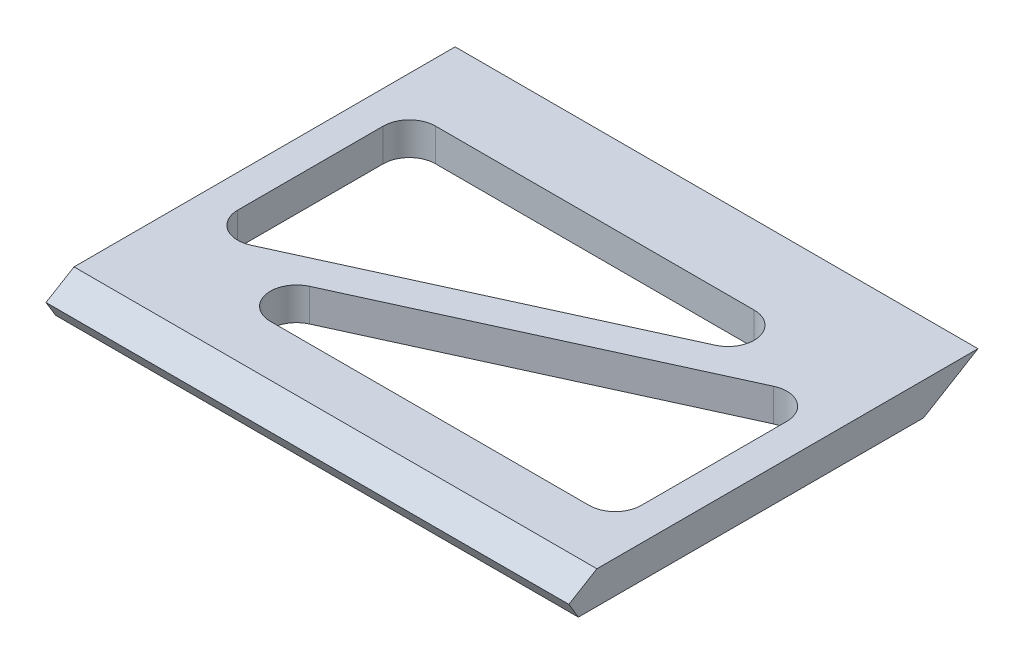
SolidWorks part; units mm, degrees
material "Balsa"
ref_plane "Front Plane" through (0, 0, 0) normal (0, 0, 1) x (1, 0, 0)
ref_plane "Top Plane" through (0, 0, 0) normal (0, 1, 0) x (1, 0, 0)
ref_plane "Right Plane" through (0, 0, 0) normal (1, 0, 0) x (0, 0, -1)
sketch "Sketch3" plane through (72.8433, 0, 0) normal (1, 0, 0) x (0, 0, -1)
  line L0 (56.968, 6.35) -> (46.3846, 0)
  line L1 (46.3846, 0) -> (-20.6804, 0)
  line L2 (-20.6804, 0) -> (-22.5302, 3.083)
  line L3 (-22.5302, 3.083) -> (-29.8236, 15.2385) construction
  line L4 (56.968, 6.35) -> (63.7199, 10.4011) construction
  line L6 (-22.5302, 3.083) -> (-17.0851, 6.35)
  line L7 (-17.0851, 6.35) -> (56.968, 6.35)
extrude "Boss-Extrude2" add sketch "Sketch3" against normal up to surface (101.6 mm away)
sketch "Sketch4" plane through (0, 6.35, 0) normal (0, 1, 0) x (1, 0, 0)
  line L0 (-28.7567, -17.0851) -> (-28.7567, 56.968) construction
  line L1 (-17.3267, 41.728) -> (44.599, 41.728)
  line L2 (-22.4067, 36.648) -> (-22.4067, 8.3732)
  line L3 (-0.5124, -7.1791) -> (61.4133, -7.1791)
  line L4 (66.4933, 26.1757) -> (66.4933, -2.0991)
  line L5 (-28.7567, 56.968) -> (72.8433, 56.968) construction
  line L6 (72.8433, 56.968) -> (72.8433, -17.0851) construction
  line L7 (-28.7567, -17.0851) -> (72.8433, -17.0851) construction
  line L8 (-15.2168, 3.7521) -> (46.7089, 32.0269)
  line L9 (-2.6224, 2.522) -> (59.3033, 30.7968)
  line L10 (-29.327, -6.1809) -> (68.931, 38.683)
  arc A0 (-2.6224, 2.522) -> (-0.5124, -7.1791) centre (-0.5124, -2.0991) ccw
  arc A1 (61.4133, -7.1791) -> (66.4933, -2.0991) centre (61.4133, -2.0991) ccw
  arc A2 (59.3033, 30.7968) -> (66.4933, 26.1757) centre (61.4133, 26.1757) cw
  arc A3 (46.7089, 32.0269) -> (44.599, 41.728) centre (44.599, 36.648) ccw
  arc A4 (-17.3267, 41.728) -> (-22.4067, 36.648) centre (-17.3267, 36.648) ccw
  arc A5 (-15.2168, 3.7521) -> (-22.4067, 8.3732) centre (-17.3267, 8.3732) cw
  dimension "D7" = 5.08
  dimension "D1" = 6.35
  dimension "D2" = 15.24
  dimension "D3" = 6.35
  dimension "D4" = 9.906
  dimension "D5" = 3.175
  dimension "D6" = 3.175
extrude "Cut-Extrude1" cut sketch "Sketch4" against normal up to surface (6.35 mm away) contours A5 L8 A3 L1 A4 L2 | A2 L9 A0 L3 A1 L4 region at (5.7835, 6.35, -27.6167) region at (38.3031, 6.35, -6.9321) up to face at (22.0433, 0, -12.8521)
